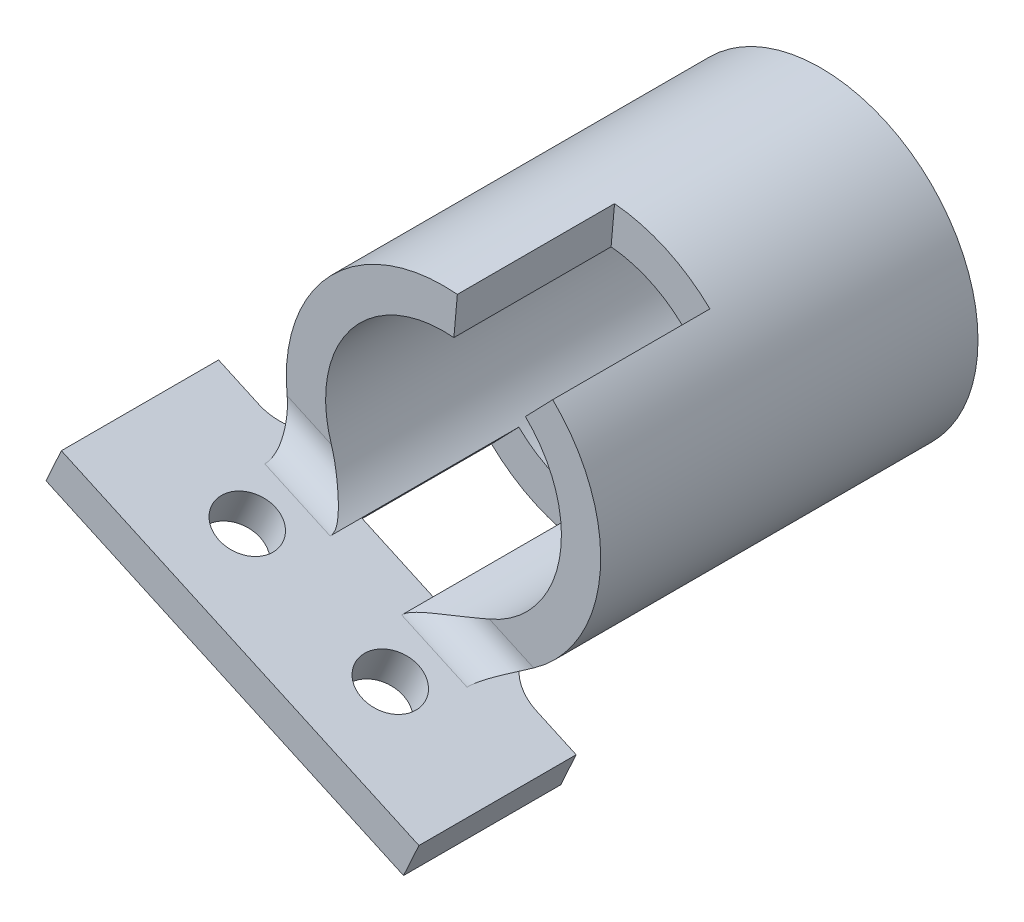
SolidWorks part; units mm, degrees
note: The reader was unsure of these and kept them because the rebuilt part matched: shared geometry of "Sketch1<3>".
ref_plane "Front Plane" through (0, 0, 0) normal (0, 0, 1) x (1, 0, 0)
ref_plane "Top Plane" through (0, 0, 0) normal (0, 1, 0) x (1, 0, 0)
ref_plane "Right Plane" through (0, 0, 0) normal (1, 0, 0) x (0, 0, -1)
sketch "Sketch1" plane through (0, 0, 0) normal (0, 0, 1) x (1, 0, 0)
  circle A0 centre (0, 0) radius 3.285
  circle A1 centre (0, 0) radius 10
  circle A2 centre (0, 0) radius 7.5
  dimension "D1" = 6.57
  dimension "D2" = 20
  dimension "D3" = 15
extrude "Boss-Extrude1" add sketch "Sketch1" along normal blind 2 contours A2 A0
extrude "Boss-Extrude2" add sketch "Sketch1<3>" along normal blind 14 contours A1 A2
sketch "Sketch1<3>" plane through (0, 0, 0) normal (0, 0, 1) x (1, 0, 0) same geometry as "Sketch1"
sketch "Sketch2" plane through (0, 0, 14) normal (0, 0, 1) x (1, 0, 0)
  line L0 (-6.946, -7.194) -> (-5.2095, -5.3955)
  line L1 (5.2095, 5.3955) -> (6.946, 7.194)
  line L2 (0.6605, 7.4709) -> (0.8807, 9.9611)
  line L3 (-0.6605, -7.4709) -> (-0.8807, -9.9611)
  line L4 (0.6605, 7.4709) -> (5.2095, 5.3955) construction
  line L5 (-5.2095, -5.3955) -> (-0.6605, -7.4709) construction
  circle A0 centre (0, 0) radius 10 construction
  circle A1 centre (0, 0) radius 7.5 construction
  circle A2 centre (0, 0) radius 10
  circle A3 centre (0, 0) radius 7.5
  circle M1 centre (0, 0) radius 7.5
  circle M2 centre (0, 0) radius 10
  dimension "D1" = 5
  dimension "D2" = 5
extrude "Boss-Extrude3" add sketch "Sketch2" along normal blind 10 contours L2 L0 M1 M2 | L3 L1 M1 M2
sketch "Sketch3" plane through (0, 0, 24) normal (0, 0, 1) x (1, 0, 0)
  line L0 (-1.8901, -9.5006) -> (-7.9554, -6.7335) construction
  line L2 (-0.6605, -7.4709) -> (-45490.0559, 20746.2014) construction
  line L3 (8.4373, -11.6216) -> (7.459, -13.766)
  line L4 (-14.3074, -1.2448) -> (-15.2857, -3.3891)
  line L5 (-14.3074, -1.2448) -> (8.4373, -11.6216)
  line L6 (7.459, -13.766) -> (-15.2857, -3.3891)
  dimension "D1" = 10
  dimension "D2" = 10
extrude "Boss-Extrude4" add sketch "Sketch3" along normal blind 10
sketch "Sketch4" plane through (-3.9133, -8.5776, 0) normal (-0.4151, -0.9098, 0) x (0.9098, -0.4151, 0)
  line L0 (-12.5, 29) -> (12.5, 29) construction
  line L1 (-12.5, 34) -> (-12.5, 24) construction
  line L2 (12.5, 34) -> (12.5, 24) construction
  line L3 (0, 34) -> (0, 24) construction
  line L4 (-12.5, 34) -> (12.5, 34) construction
  line L5 (-3.3333, 24) -> (3.3333, 24) construction
  circle A0 centre (-5, 29) radius 1.8
  circle A1 centre (5, 29) radius 1.8
  dimension "D1" = 3.6
  dimension "D2" = 3.6
  dimension "D3" = 5
  dimension "D4" = 5
extrude "Cut-Extrude1" cut sketch "Sketch4" against normal blind 10
fillet "Fillet1" radius 2 2 edges at (-7.2888, -4.4468, 24) (1.4188, -8.4195, 24)
fillet "Fillet2" radius 2 1 edges at (1.3419, -9.9096, 24)
